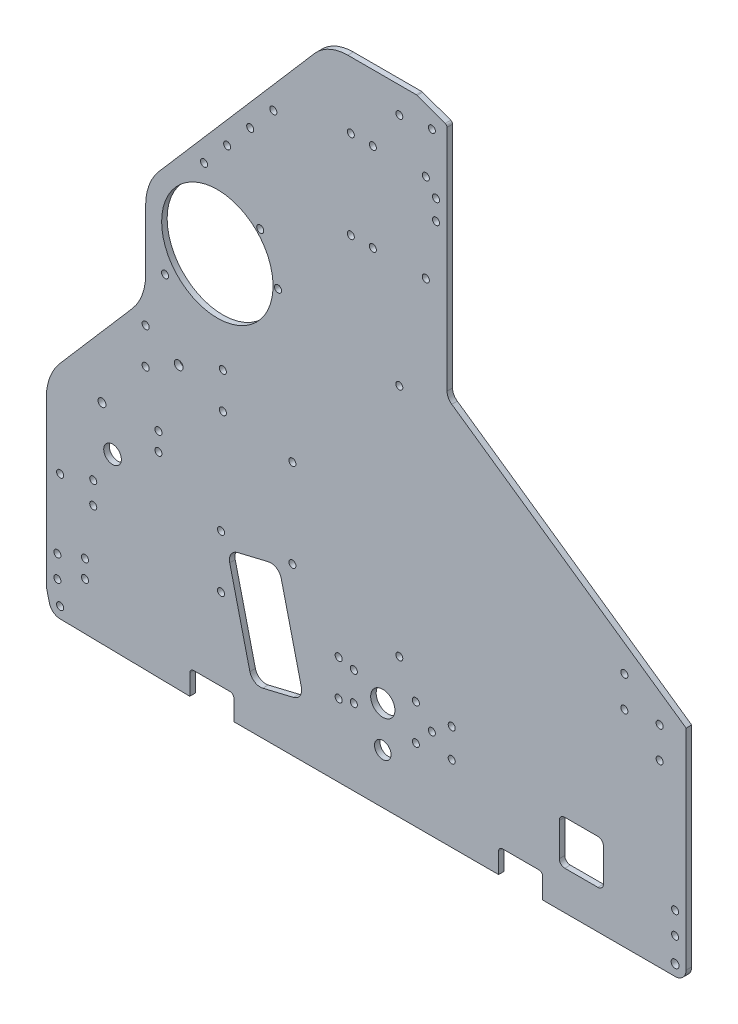
SolidWorks part; units mm, degrees
ref_plane "Front Plane" through (0, 0, 0) normal (0, 0, 1) x (1, 0, 0)
ref_plane "Top Plane" through (0, 0, 0) normal (0, 1, 0) x (1, 0, 0)
ref_plane "Right Plane" through (0, 0, 0) normal (1, 0, 0) x (0, 0, -1)
sketch "Sketch1" plane through (0, 0, 0) normal (0, 0, 1) x (1, 0, 0)
  line L0 (82.55, -20.32) -> (82.55, -6.35)
  line L2 (0, 0) -> (0, 157.48)
  line L4 (368.3, -20.32) -> (368.3, 106.68)
  line L5 (82.55, -6.35) -> (107.95, -6.35)
  line L6 (107.95, -6.35) -> (107.95, -20.32)
  line L7 (107.95, -20.32) -> (260.35, -20.32)
  line L8 (260.35, -20.32) -> (260.35, -6.35)
  line L9 (260.35, -6.35) -> (285.75, -6.35)
  line L10 (285.75, -6.35) -> (285.75, -20.32)
  line L11 (285.75, -20.32) -> (368.3, -20.32)
  line L12 (361.95, 12.7) -> (368.3, 12.7) construction
  line L13 (0, 0) -> (6.35, 0) construction
  line L14 (0.1896, -7.8901) -> (1.7771, -14.2401)
  line L15 (7.8295, -19.0491) -> (82.55, -20.32)
  line L16 (0, 0) -> (0, -6.35)
  line L17 (76.2, 141.605) -> (79.375, 141.605) construction
  line L18 (57.15, 131.2863) -> (101.6, 131.2862) construction
  line L19 (57.15, 131.2863) -> (57.15, 151.9238) construction
  line L20 (101.6, 131.2862) -> (101.6, 151.9237) construction
  line L21 (57.15, 151.9238) -> (101.6, 151.9237) construction
  line L22 (57.15, 131.2863) -> (101.6, 151.9237) construction
  line L23 (101.6, 131.2862) -> (57.15, 151.9238) construction
  line L25 (203.2, 59.805) -> (203.2, 194.805) construction
  line L26 (203.2, 194.805) -> (203.2, 329.805) construction
  line L27 (355.6, 332.105) -> (330.2, 332.105) construction
  line L28 (330.2, 332.105) -> (330.2, 217.805) construction
  line L29 (330.2, 217.805) -> (355.6, 217.805) construction
  line L30 (355.6, 217.805) -> (355.6, 332.105) construction
  line L31 (203.2, 344.805) -> (203.2, 194.805) construction
  line L32 (50.8, 332.105) -> (76.2, 332.105) construction
  line L33 (76.2, 332.105) -> (76.2, 217.805) construction
  line L34 (50.8, 217.805) -> (50.8, 332.105) construction
  line L35 (76.2, 217.805) -> (50.8, 217.805) construction
  line L36 (213.2, 344.805) -> (230.6638, 338.455)
  line L37 (203.2, 344.805) -> (161.925, 344.805)
  line L38 (203.2, 344.805) -> (213.2, 344.805)
  line L39 (348.5362, 344.805) -> (413.4623, 344.805)
  line L40 (348.5362, 344.805) -> (230.6638, 344.805) construction
  line L42 (161.925, 344.805) -> (0, 157.48)
  line L44 (230.6638, 338.455) -> (230.6638, 202.565)
  line L45 (230.6638, 202.565) -> (368.3, 106.68)
  line L46 (213.2, 344.805) -> (-141.0713, 344.805) construction
  circle A0 centre (6.35, 0) radius 2.032
  circle A1 centre (6.35, 12.7) radius 2.032
  circle A2 centre (361.95, 0) radius 2.032
  circle A3 centre (361.95, 12.7) radius 2.032
  arc A5 (1.7771, -14.2401) -> (7.8295, -19.0491) centre (7.9375, -12.7) ccw
  circle A6 centre (7.9375, -12.7) radius 2.032
  arc A7 (0, -6.35) -> (0.1896, -7.8901) centre (6.35, -6.35) ccw
  circle A8 centre (38.1, 78.105) radius 5.08
  circle A9 centre (76.2, 141.605) radius 2.54
  circle A10 centre (101.6, 131.2862) radius 2.032
  circle A11 centre (101.6, 151.9237) radius 2.032
  circle A12 centre (57.15, 151.9238) radius 2.032
  circle A13 centre (57.15, 131.2863) radius 2.032
  circle A15 centre (203.2, 59.805) radius 2
  circle A16 centre (203.2, 194.805) radius 2
  circle A17 centre (203.2, 329.805) radius 2
  circle A18 centre (63.5, 313.055) radius 2.032
  circle A20 centre (355.6, 332.105) radius 2.032
  circle A21 centre (330.2, 332.105) radius 2.032
  circle A22 centre (355.6, 217.805) radius 2.032
  circle A23 centre (330.2, 217.805) radius 2.032
  circle A24 centre (50.8, 332.105) radius 2.032
  circle A25 centre (76.2, 332.105) radius 2.032
  circle A26 centre (50.8, 217.805) radius 2.032
  circle A27 centre (76.2, 217.805) radius 2.032
  circle A28 centre (221.9319, 332.105) radius 2
  circle A29 centre (224.3138, 298.831) radius 2.032
  circle A30 centre (353.06, 100.7351) radius 2.032
  circle A31 centre (332.74, 115.9751) radius 2.032
  circle A32 centre (332.74, 98.1951) radius 2.032
  circle A33 centre (353.06, 82.9551) radius 2.032
  circle A34 centre (117.3562, 280.4276) radius 2.032
  circle A35 centre (104.0678, 265.0548) radius 2.032
  circle A36 centre (90.7795, 249.682) radius 2.032
  circle A38 centre (130.6445, 295.8004) radius 2.032
  circle A39 centre (68.326, 182.9237) radius 2.032
  circle A40 centre (224.3138, 287.401) radius 2.032
  point P82 (203.2, 344.805)
  point P83 (221.9319, 341.63)
  point P90 (368.3, 62.484)
  dimension "D6" = 4.064
  dimension "D10" = 6.35
  dimension "D11" = 4.064
  dimension "D17" = 38.1
  dimension "D27" = 4
  dimension "D31" = 4.064
  dimension "D32" = 41.275
  dimension "D36" = 4.064
  dimension "D47" = 39.624
  dimension "D48" = 4.064
  dimension "D25" = 5.08
  dimension "D26" = 4.064
  dimension "D52" = 4.064
  dimension "D65" = 4.064
  dimension "D69" = 10.16
  dimension "D2" = 127
  dimension "D3" = 13.97
  dimension "D4" = 25.4
  dimension "D5" = 152.4
  dimension "D7" = 12.7
  dimension "D8" = 6.35
  dimension "D9" = 20.32
  dimension "D12" = 12.7
  dimension "D13" = 1.5875
  dimension "D14" = 82.55
  dimension "D15" = 368.3
  dimension "D16" = 6.35
  dimension "D18" = 98.425
  dimension "D19" = 38.1
  dimension "D20" = 63.5
  dimension "D21" = 3.175
  dimension "D22" = 270
  dimension "D23" = 20.6375
  dimension "D24" = 44.45
  dimension "D28" = 135
  dimension "D29" = 12.7
  dimension "D30" = 15
  dimension "D33" = 63.5
  dimension "D34" = 27.4638
  dimension "D35" = 12.7
  dimension "D37" = 114.3
  dimension "D38" = 25.4
  dimension "D39" = 12.7
  dimension "D40" = 157.48
  dimension "D41" = 142.24
  dimension "D42" = 365.125
  dimension "D43" = 10
  dimension "D44" = 6.35
  dimension "D45" = 31.75
  dimension "D46" = 6.35
  dimension "D49" = 6.35
  dimension "D50" = 203.2
  dimension "D51" = 15.24
  dimension "D53" = 17.78
  dimension "D54" = 17.78
  dimension "D55" = 20.32
  dimension "D56" = 15.24
  dimension "D57" = 92.202
  dimension "D58" = 8.382
  dimension "D59" = 20.32
  dimension "D60" = 20.32
  dimension "D61" = 8.382
  dimension "D62" = 20.32
  dimension "D63" = 8.382
  dimension "D64" = 8.382
  dimension "D66" = 35.052
  dimension "D67" = 68.326
  dimension "D68" = 11.43
extrude "Boss-Extrude1" add sketch "Sketch1" along normal blind 3.175 contours L16 A7 L14 A5 L15 L2 A0 A1 A6 region at (171.4477, 119.555, 0)
fillet "Fillet1" radius 2.286 4 edges at (285.75, -6.35, 1.5875) (107.95, -6.35, 1.5875) (260.35, -6.35, 1.5875) (82.55, -6.35, 1.5875)
fillet "Fillet2" radius 6.35 1 edges at (230.6638, 202.565, 1.5875)
sketch "Sketch2" plane through (0, 0, 0) normal (0, 0, -1) x (-1, 0, 0)
  circle A0 centre (-100.5528, 71.086) radius 2.032 construction
  circle A1 centre (-100.5528, 40.606) radius 2.032 construction
  circle A2 centre (-22.225, 18.2025) radius 2.032 construction
  circle A3 centre (-22.225, 8.0425) radius 2.032 construction
  circle A4 centre (-100.5528, 71.086) radius 2.032
  circle A5 centre (-100.5528, 40.606) radius 2.032
  circle A6 centre (-22.225, 18.2025) radius 2.032
  circle A7 centre (-22.225, 8.0425) radius 2.032
extrude "Cut-Extrude1" cut sketch "Sketch2" against normal through all
fillet "Fillet3" radius 1.5875 2 edges at (230.6638, 338.455, 1.5875) (213.2, 344.805, 1.5875)
sketch "Sketch3" plane through (0, 0, 3.175) normal (0, 0, 1) x (1, 0, 0)
  line L0 (132.9524, 63.2646) -> (132.7215, 64.2281) construction
  line L1 (128.3814, 66.8897) -> (110.6828, 62.6472) construction
  line L2 (114.5132, 58.4237) -> (126.8822, 61.3887) construction
  line L3 (108.0212, 58.3071) -> (108.2522, 57.3436) construction
  line L4 (131.2006, 57.703) -> (140.0164, 20.9265) construction
  line L5 (144.0993, 16.7636) -> (132.9524, 63.2646) construction
  line L6 (108.2522, 57.3436) -> (119.3991, 10.8426) construction
  line L7 (121.1509, 16.4042) -> (112.3351, 53.1807) construction
  line L8 (119.3991, 10.8426) -> (119.6301, 9.8791) construction
  line L9 (144.3303, 15.8001) -> (144.0993, 16.7636) construction
  line L10 (137.8383, 15.6835) -> (125.4694, 12.7185) construction
  line L11 (123.9701, 7.2175) -> (141.6687, 11.4601) construction
  line L12 (132.9524, 63.2646) -> (132.7215, 64.2281)
  line L13 (128.3814, 66.8897) -> (110.6828, 62.6472)
  line L14 (114.5132, 58.4237) -> (126.8822, 61.3887)
  line L15 (108.0212, 58.3071) -> (108.2522, 57.3436)
  line L16 (131.2006, 57.703) -> (140.0164, 20.9265)
  line L17 (144.0993, 16.7636) -> (132.9524, 63.2646)
  line L18 (108.2522, 57.3436) -> (119.3991, 10.8426)
  line L19 (121.1509, 16.4042) -> (112.3351, 53.1807)
  line L20 (119.3991, 10.8426) -> (119.6301, 9.8791)
  line L21 (144.3303, 15.8001) -> (144.0993, 16.7636)
  line L22 (137.8383, 15.6835) -> (125.4694, 12.7185)
  line L23 (123.9701, 7.2175) -> (141.6687, 11.4601)
  line L24 (127.7894, 69.3598) -> (110.0908, 65.1172)
  line L25 (105.5512, 57.715) -> (105.7822, 56.7515)
  line L26 (105.7822, 56.7515) -> (116.9291, 10.2505)
  line L27 (116.9291, 10.2505) -> (117.16, 9.287)
  line L28 (124.5622, 4.7475) -> (142.2608, 8.99)
  line L29 (146.8003, 16.3922) -> (146.5694, 17.3557)
  line L30 (146.5694, 17.3557) -> (135.4225, 63.8567)
  line L31 (135.4225, 63.8567) -> (135.1915, 64.8202)
  line L32 (14.605, -0.1369) -> (103.7278, 32.3011) construction
  line L33 (14.605, -0.1369) -> (103.7278, 32.3011)
  line L34 (0, -6.35) -> (0, 157.48) construction
  line L35 (-39.6666, 74.7152) -> (103.7278, 126.9065) construction
  line L36 (26.9875, 46.9531) -> (26.9875, 59.6531) construction
  line L37 (107.95, -20.32) -> (260.35, -20.32) construction
  line L38 (64.5259, 92.5258) -> (64.5259, 102.9405) construction
  arc A0 (132.7215, 64.2281) -> (128.6308, 66.9403) centre (129.2206, 63.3889) ccw construction
  arc A1 (110.6828, 62.6472) -> (110.4377, 62.5791) centre (111.522, 59.1463) ccw construction
  arc A2 (128.6308, 66.9403) -> (128.3814, 66.8897) centre (129.2206, 63.3889) ccw construction
  arc A3 (110.4377, 62.5791) -> (108.0212, 58.3071) centre (111.522, 59.1463) ccw construction
  arc A4 (119.6301, 9.8791) -> (123.7207, 7.1669) centre (123.1309, 10.7183) ccw construction
  arc A5 (141.9139, 11.5281) -> (144.3303, 15.8001) centre (140.8295, 14.9609) ccw construction
  arc A6 (141.6687, 11.4601) -> (141.9139, 11.5281) centre (140.8295, 14.9609) ccw construction
  arc A7 (123.7207, 7.1669) -> (123.9701, 7.2175) centre (123.1309, 10.7183) ccw construction
  arc A8 (132.7215, 64.2281) -> (128.6308, 66.9403) centre (129.2206, 63.3889) ccw
  arc A9 (110.6828, 62.6472) -> (110.4377, 62.5791) centre (111.522, 59.1463) ccw
  arc A10 (128.6308, 66.9403) -> (128.3814, 66.8897) centre (129.2206, 63.3889) ccw
  arc A11 (110.4377, 62.5791) -> (108.0212, 58.3071) centre (111.522, 59.1463) ccw
  arc A12 (119.6301, 9.8791) -> (123.7207, 7.1669) centre (123.1309, 10.7183) ccw
  arc A13 (141.9139, 11.5281) -> (144.3303, 15.8001) centre (140.8295, 14.9609) ccw
  arc A14 (141.6687, 11.4601) -> (141.9139, 11.5281) centre (140.8295, 14.9609) ccw
  arc A15 (123.7207, 7.1669) -> (123.9701, 7.2175) centre (123.1309, 10.7183) ccw
  arc A16 (110.0908, 65.1172) -> (109.6726, 65.0012) centre (111.522, 59.1463) ccw
  arc A17 (109.6726, 65.0012) -> (105.5512, 57.715) centre (111.522, 59.1463) ccw
  arc A18 (117.16, 9.287) -> (124.1369, 4.6613) centre (123.1309, 10.7183) ccw
  arc A19 (124.1369, 4.6613) -> (124.5622, 4.7475) centre (123.1309, 10.7183) ccw
  arc A20 (142.2608, 8.99) -> (142.6789, 9.1061) centre (140.8295, 14.9609) ccw
  arc A21 (142.6789, 9.1061) -> (146.8003, 16.3922) centre (140.8295, 14.9609) ccw
  arc A22 (135.1915, 64.8202) -> (128.2147, 69.446) centre (129.2206, 63.3889) ccw
  arc A23 (128.2147, 69.446) -> (127.7894, 69.3598) centre (129.2206, 63.3889) ccw
  circle A26 centre (133.35, 208.2281) radius 2.032 construction
  circle A33 centre (26.9875, 46.9531) radius 2.032
  circle A34 centre (26.9875, 59.6531) radius 2.032
  circle A35 centre (7.9375, 53.3031) radius 2.032
  circle A37 centre (32.0306, 100.8109) radius 31.75 construction
  circle A38 centre (32.0306, 100.8109) radius 2.286
  circle A39 centre (123.1207, 232.9238) radius 2.032 construction
  circle A40 centre (64.5259, 102.9405) radius 2.032
  circle A41 centre (64.5259, 92.5258) radius 2.032
  circle A42 centre (133.35, 208.2281) radius 2.032
  circle A43 centre (123.1207, 232.9238) radius 2.032
  ellipse E0 centre (124.5974, 48.8487) end of major axis (128.5376, 61.3578) minor radius 6 (131.2006, 57.703) -> (126.8822, 61.3887) ccw construction
  ellipse E1 centre (122.2349, 48.2824) end of major axis (113.0518, 57.6456) minor radius 6 (114.5132, 58.4237) -> (112.3351, 53.1807) ccw construction
  ellipse E2 centre (127.7541, 25.2585) end of major axis (131.6942, 37.7675) minor radius 6 (121.1509, 16.4042) -> (125.4694, 12.7185) ccw construction
  ellipse E3 centre (130.1166, 25.8248) end of major axis (139.2998, 16.4616) minor radius 6 (137.8383, 15.6835) -> (140.0164, 20.9265) ccw construction
  ellipse E4 centre (124.5974, 48.8487) end of major axis (120.6573, 36.3397) minor radius 6 (131.2006, 57.703) -> (126.8822, 61.3887) ccw
  ellipse E5 centre (122.2349, 48.2824) end of major axis (131.4181, 38.9192) minor radius 6 (114.5132, 58.4237) -> (112.3351, 53.1807) ccw
  ellipse E6 centre (127.7541, 25.2585) end of major axis (131.6942, 37.7675) minor radius 6 (121.1509, 16.4042) -> (125.4694, 12.7185) ccw
  ellipse E7 centre (130.1166, 25.8248) end of major axis (139.2998, 16.4616) minor radius 6 (137.8383, 15.6835) -> (140.0164, 20.9265) ccw
  point P93 (26.9875, 53.3031)
  point P115 (32.0306, 100.8109)
  dimension "D3" = 63.5
  dimension "D4" = 4.572
  dimension "D8" = 4.064
  dimension "D2" = 88.9
  dimension "D5" = 7.9375
  dimension "D6" = 19.05
  dimension "D7" = 73.6231
  dimension "D9" = 12.7
  dimension "D10" = 10.4147
  dimension "D11" = 37.5384
  dimension "D12" = 45.5727
  dimension "D1" = 2.54
extrude "Cut-Extrude2" cut sketch "Sketch3" against normal through all contours A22 A23 L24 A16 A17 L25 L26 L27 A18 A19 L28 A20 A21 L29 L30 L31 A15 A12 L20 L18 L15 A11 A9 L13 A10 A8 L12 L17 L21 A13 A14 L23 | A12 A15 L23 A14 A13 L21 L17 L12 A8 A10 L13 A9 A11 L15 L18 L20 E7 L22 E6 L19 E5 L14 E4 L16 | L22 E7 L16 E4 L14 E5 L19 E6 | A38 | A41 | A40 | A35 | A34 | A33 | A43 | A42 region at (137.844, 39.8506, 3.175) region at (126.1758, 37.0536, 3.175) region at (128.1544, 68.6507, 3.175) region at (32.0306, 100.8109, 3.175) region at (64.5259, 102.9405, 3.175) region at (64.5259, 92.5258, 3.175)
sketch "Sketch4" plane through (0, 0, 3.175) normal (0, 0, 1) x (1, 0, 0)
  line L0 (57.15, 151.9238) -> (101.6, 151.9237) construction
  line L1 (168.275, 21.4312) -> (212.725, 21.4312) construction
  line L2 (168.275, 21.4312) -> (168.275, 42.0687) construction
  line L3 (168.275, 42.0687) -> (212.725, 42.0687) construction
  line L4 (212.725, 21.4312) -> (212.725, 42.0687) construction
  line L5 (168.275, 21.4312) -> (212.725, 42.0687) construction
  line L6 (168.275, 42.0687) -> (212.725, 21.4312) construction
  line L7 (57.15, 131.2863) -> (57.15, 151.9238) construction
  line L8 (107.95, -20.32) -> (260.35, -20.32) construction
  line L9 (193.675, 31.75) -> (177.005, 31.75) construction
  line L10 (190.5, 31.75) -> (193.675, 31.75) construction
  line L11 (6.35, 12.7) -> (361.95, 12.7) construction
  line L12 (107.95, -6.35) -> (107.95, -20.32) construction
  line L13 (193.675, 31.75) -> (220.6625, 31.75) construction
  line L14 (177.005, 23.4569) -> (177.005, 40.0431) construction
  line L15 (213.2, 44.805) -> (193.2, 44.805) construction
  line L16 (213.2, 44.805) -> (213.2, 344.805) construction
  line L17 (213.2, 344.805) -> (193.2, 344.805) construction
  line L18 (193.2, 44.805) -> (193.2, 344.805) construction
  line L19 (213.2, 44.805) -> (193.2, 344.805) construction
  line L20 (213.2, 344.805) -> (193.2, 44.805) construction
  line L21 (226.9319, 332.105) -> (226.9319, 31.75) construction
  line L22 (237.33, 40.0431) -> (233.3612, 40.0431) construction
  line L23 (237.33, 23.4569) -> (233.3612, 23.4569) construction
  circle A0 centre (168.275, 42.0687) radius 2.032
  circle A1 centre (212.725, 42.0687) radius 2.032
  circle A2 centre (212.725, 21.4312) radius 2.032
  circle A3 centre (168.275, 21.4312) radius 2.032
  circle A4 centre (193.675, 31.75) radius 6.985
  circle A7 centre (220.6625, 31.75) radius 14.2875 construction
  circle A8 centre (193.675, 31.75) radius 12.7 construction
  circle A9 centre (177.005, 40.0431) radius 2.032
  circle A10 centre (177.005, 23.4569) radius 2.032
  circle A11 centre (237.33, 40.0431) radius 2.032 construction
  circle A12 centre (237.33, 23.4569) radius 2.032 construction
  circle A13 centre (193.675, 8.4667) radius 4.7625
  circle A14 centre (221.9319, 31.75) radius 2.032
  circle A15 centre (221.9319, 31.75) radius 5 construction
  circle A16 centre (221.9319, 332.105) radius 5 construction
  circle A17 centre (233.3612, 23.4569) radius 2.032
  circle A18 centre (233.3612, 40.0431) radius 2.032
  point P0 (190.5, 31.75)
  point P26 (203.2, 194.805)
  point P38 (177.005, 31.75)
  dimension "D1" = 4.064
  dimension "D4" = 13.97
  dimension "D7" = 9.525
  dimension "D10" = 25.4
  dimension "D11" = 28.575
  dimension "D16" = 10
  dimension "D17" = 4.064
  dimension "D18" = 10
  dimension "D2" = 52.07
  dimension "D3" = 3.175
  dimension "D5" = 82.55
  dimension "D6" = 26.9875
  dimension "D8" = 20
  dimension "D9" = 300
  dimension "D12" = 16.67
  dimension "D13" = 16.5862
  dimension "D14" = 60.325
  dimension "D15" = 23.2833
  dimension "D19" = 3.9688
extrude "Cut-Extrude3" cut sketch "Sketch4" against normal through all
sketch "Sketch5" plane through (0, 0, 0) normal (0, 0, -1) x (-1, 0, 0)
  line L0 (-57.15, 223.5947) -> (-57.15, 165.3337)
  line L1 (-161.925, 344.805) -> (-52.7201, 218.4699) construction
  line L2 (-57.15, 165.3337) -> (0, 99.219)
  line L3 (0, -6.35) -> (0, 157.48) construction
  line L5 (-50.4199, 215.8089) -> (0, 157.48) construction
  line L6 (-57.15, 223.5947) -> (0, 157.48)
  line L7 (0, 157.48) -> (0, 99.219)
  line L8 (-361.95, -13.97) -> (-368.3, -13.97) construction
  line L9 (-361.95, -13.97) -> (-361.95, -20.32) construction
  line L10 (-285.75, -20.32) -> (-368.3, -20.32) construction
  line L11 (-368.3, -20.32) -> (-368.3, 106.68) construction
  circle A0 centre (-98.425, 208.2281) radius 32.0675
  circle A2 centre (-361.95, -13.97) radius 2.286
  dimension "D3" = 64.135
  dimension "D7" = 4.572
  dimension "D1" = 38.1
  dimension "D2" = 57.15
  dimension "D4" = 41.275
  dimension "D5" = 41.275
  dimension "D6" = 6.35
extrude "Cut-Extrude5" cut sketch "Sketch5" against normal through all contours A0 | L7 L6 L0 L2 | A2 region at (28.575, 161.4068, 0) region at (98.425, 208.2281, 0)
fillet "Fillet4" radius 31.75 3 edges at (0, 99.219, 1.5875) (57.15, 165.3337, 1.5875) (57.15, 223.5947, 1.5875)
sketch "Sketch6" plane through (0, 0, 3.175) normal (0, 0, 1) x (1, 0, 0)
  line L0 (285.75, -20.32) -> (368.3, -20.32) construction
  line L1 (298.45, 27.305) -> (317.5, 27.305)
  line L2 (295.275, 24.13) -> (295.275, 5.08)
  line L3 (298.45, 1.905) -> (317.5, 1.905)
  line L4 (320.675, 24.13) -> (320.675, 5.08)
  line L5 (295.275, 27.305) -> (320.675, 1.905) construction
  line L6 (295.275, 1.905) -> (320.675, 27.305) construction
  line L7 (368.3, -20.32) -> (368.3, 106.68) construction
  arc A0 (295.275, 5.08) -> (298.45, 1.905) centre (298.45, 5.08) ccw
  arc A1 (317.5, 1.905) -> (320.675, 5.08) centre (317.5, 5.08) ccw
  arc A2 (317.5, 27.305) -> (320.675, 24.13) centre (317.5, 24.13) cw
  arc A3 (298.45, 27.305) -> (295.275, 24.13) centre (298.45, 24.13) ccw
  point P0 (307.975, 14.605)
  dimension "D2" = 3.175
  dimension "D1" = 25.4
  dimension "D3" = 22.225
  dimension "D4" = 47.625
extrude "Cut-Extrude6" cut sketch "Sketch6" against normal through all
fillet "Fillet5" radius 25.4 1 edges at (161.925, 344.805, 1.5875)
sketch "Sketch8" plane through (0, 0, 0) normal (0, 0, -1) x (-1, 0, 0)
  circle A0 centre (-187.96, 306.705) radius 2.032 construction
  arc A1 (-176.3652, 304.9998) -> (-176.3652, 308.4102) centre (-175.26, 306.705) ccw construction
  arc A2 (-219.0586, 304.7695) -> (-219.0586, 308.6405) centre (-218.44, 306.705) ccw construction
  circle A3 centre (-205.74, 306.705) radius 2.032 construction
  arc A4 (-219.0586, 253.9695) -> (-219.0586, 257.8405) centre (-218.44, 255.905) ccw construction
  circle A5 centre (-205.74, 255.905) radius 2.032 construction
  circle A6 centre (-187.96, 255.905) radius 2.032 construction
  arc A7 (-176.3652, 254.1998) -> (-176.3652, 257.6102) centre (-175.26, 255.905) ccw construction
  circle A8 centre (-187.96, 306.705) radius 2.032
  arc A9 (-176.3652, 304.9998) -> (-176.3652, 308.4102) centre (-175.26, 306.705) ccw
  arc A10 (-219.0586, 304.7695) -> (-219.0586, 308.6405) centre (-218.44, 306.705) ccw
  circle A11 centre (-205.74, 306.705) radius 2.032
  arc A12 (-219.0586, 253.9695) -> (-219.0586, 257.8405) centre (-218.44, 255.905) ccw
  circle A13 centre (-205.74, 255.905) radius 2.032
  circle A14 centre (-187.96, 255.905) radius 2.032
  arc A15 (-176.3652, 254.1998) -> (-176.3652, 257.6102) centre (-175.26, 255.905) ccw
  circle A16 centre (-218.44, 306.705) radius 2.032
  circle A17 centre (-175.26, 306.705) radius 2.032
  circle A18 centre (-175.26, 255.905) radius 2.032
  circle A19 centre (-218.44, 255.905) radius 2.032
  circle A20 centre (-218.44, 306.705) radius 3.9688
  circle A21 centre (-205.74, 306.705) radius 3.9688
  circle A22 centre (-175.26, 306.705) radius 3.9687
  circle A23 centre (-218.44, 255.905) radius 3.9688
  circle A24 centre (-205.74, 255.905) radius 3.9688
  circle A25 centre (-187.96, 255.905) radius 3.9687
  circle A26 centre (-175.26, 255.905) radius 3.9687
  circle A27 centre (-187.96, 306.705) radius 3.9687
  dimension "D1" = 7.9375
extrude "Cut-Extrude7" cut sketch "Sketch8" against normal through all contours A10 A16 | A9 A17 | A15 A18 | A12 A19 | A8 | A14 region at (175.26, 306.705, 0) region at (218.44, 306.705, 0) region at (218.44, 255.905, 0) region at (175.26, 255.905, 0)
sketch "Sketch10" plane through (0, 0, 3.175) normal (0, 0, 1) x (1, 0, 0)
  circle A4 centre (141.6425, 75.1606) radius 2.032 construction
  circle A5 centre (141.6425, 125.9606) radius 2.032 construction
  circle A6 centre (141.6425, 75.1606) radius 2.032
  circle A7 centre (141.6425, 125.9606) radius 2.032
extrude "Cut-Extrude8" cut sketch "Sketch10" against normal through all
fillet "Fillet6" radius 6.35 1 edges at (368.3, -20.32, 1.5875)
